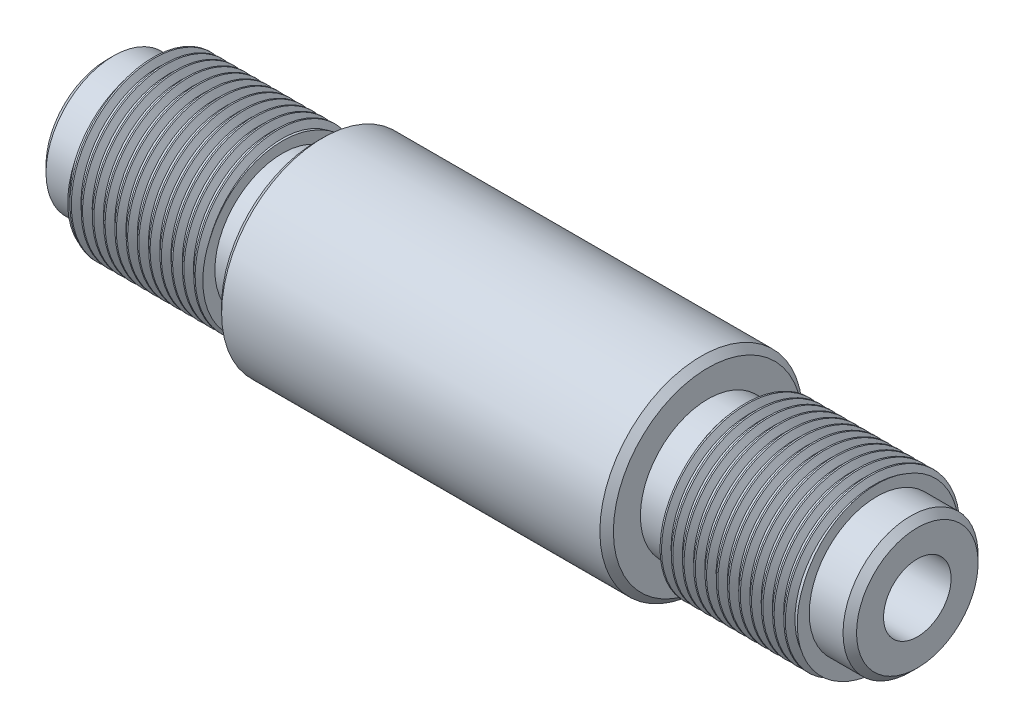
SolidWorks part; units mm, degrees
ref_plane "Front Plane" through (0, 0, 0) normal (0, 0, 1) x (1, 0, 0)
ref_plane "Top Plane" through (0, 0, 0) normal (0, 1, 0) x (1, 0, 0)
ref_plane "Right Plane" through (0, 0, 0) normal (1, 0, 0) x (0, 0, -1)
sketch "Sketch1" plane through (0, 0, 0) normal (0, 0, 1) x (1, 0, 0)
  line L0 (-46.1083, 0) -> (30.0917, 0) construction
  line L1 (-46.1083, 6.35) -> (-46.1083, 12.7)
  line L2 (-38.4883, 12.7) -> (-38.4883, 15.875)
  line L3 (-38.4883, 15.875) -> (-13.0883, 15.875)
  line L4 (-13.0883, 15.875) -> (-13.0883, 12.7)
  line L5 (-13.0883, 12.7) -> (-6.7383, 12.7)
  line L6 (-6.7383, 12.7) -> (-6.7383, 19.05)
  line L7 (-6.7383, 19.05) -> (30.0917, 19.05)
  line L8 (30.0917, 19.05) -> (30.0917, 6.35)
  line L9 (-46.1083, 12.7) -> (-38.4883, 12.7)
  line L10 (-46.1083, 6.35) -> (30.0917, 6.35)
  dimension "D1" = 76.2
  dimension "D2" = 19.05
  dimension "D3" = 6.35
  dimension "D4" = 15.875
  dimension "D5" = 12.7
  dimension "D6" = 7.62
  dimension "D7" = 33.02
  dimension "D8" = 39.37
revolve "Revolve1" add sketch "Sketch1" angle 360 about L0
thread "Thread1" pitch 2.1167 method cut profile "Thread Profile1" start angle 0, offset 1.5875, length 0, pitch 2.1167, diameter 31.75
ref_plane "Plane1" through (-40.0758, 0, -15.875) normal (0, -1, 0) x (0, 0, -1)
sketch "Thread Profile1" plane through (-40.0758, 0, -15.875) normal (0, -1, 0) x (0, 0, -1)
  line L0 (0, 0) -> (0, 2.1167) construction
  line L11 (0, 0) -> (0, 1.8521)
  line L12 (0, 1.8521) -> (-1.1457, 1.1906)
  line L13 (-1.1457, 1.1906) -> (-1.1457, 0.6615)
  line L15 (-1.1457, 0.6615) -> (0, 0)
  line L17 (-1.1457, 0.926) -> (0, 0.926) construction
  point P2 (0, 0)
  dimension "Pitch" = 2.1167
  dimension "Profile_Angle" = 60
  dimension "Profile_Land" = 0.5292
  dimension "Profile_Height" = 1.1457
mirror "Mirror1" about plane through (30.0917, 19.05, 0) normal (-1, 0, 0) of bodies 102
chamfer "Chamfer1" distance 1.27 angle 45 4 edges at (-46.1083, 0, 12.7) (-6.7383, 0, 19.05) (66.9217, 0, 19.05) (106.2917, 0, 12.7)
sketch "Sketch2" [suppressed] plane through (0, 0, 0) normal (0, 1, 0) x (1, 0, 0)
  line L0 (-53.2651, 0) -> (111.621, 0) construction
  line L2 (-53.2651, 0) -> (115.8853, 0)
  line L3 (-53.2651, 0) -> (-53.2651, -29.8501)
  line L4 (-53.2651, -29.8501) -> (115.8853, -29.8501)
  line L5 (115.8853, 0) -> (115.8853, -29.8501)
extrude "Cut-Extrude1" [suppressed] cut sketch "Sketch2" against normal through all both and the other way through all
